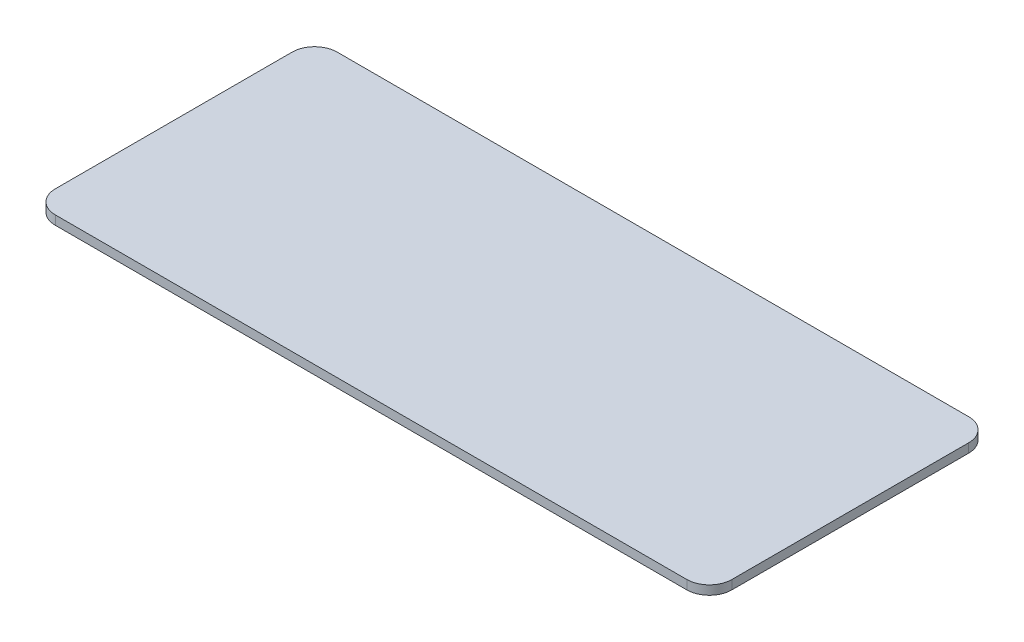
SolidWorks part; units mm, degrees
ref_plane "Front Plane" through (0, 0, 0) normal (0, 0, 1) x (1, 0, 0)
ref_plane "Top Plane" through (0, 0, 0) normal (0, 1, 0) x (1, 0, 0)
ref_plane "Right Plane" through (0, 0, 0) normal (1, 0, 0) x (0, 0, -1)
sketch "Sketch1" plane through (0, 0, 0) normal (0, 1, 0) x (1, 0, 0)
  line L1 (-60, -25) -> (60, -25)
  line L2 (-60, -25) -> (-60, 25)
  line L3 (-60, 25) -> (60, 25)
  line L4 (60, -25) -> (60, 25)
  line L5 (-60, -25) -> (60, 25) construction
  line L6 (-60, 25) -> (60, -25) construction
  point P0 (0, 0)
  dimension "D1" = 50
  dimension "D2" = 120
extrude "Boss-Extrude1" add sketch "Sketch1" along normal blind 1.6
fillet "Fillet1" radius 4 4 edges at (60, 0.8, 25) (60, 0.8, -25) (-60, 0.8, -25) (-60, 0.8, 25)
